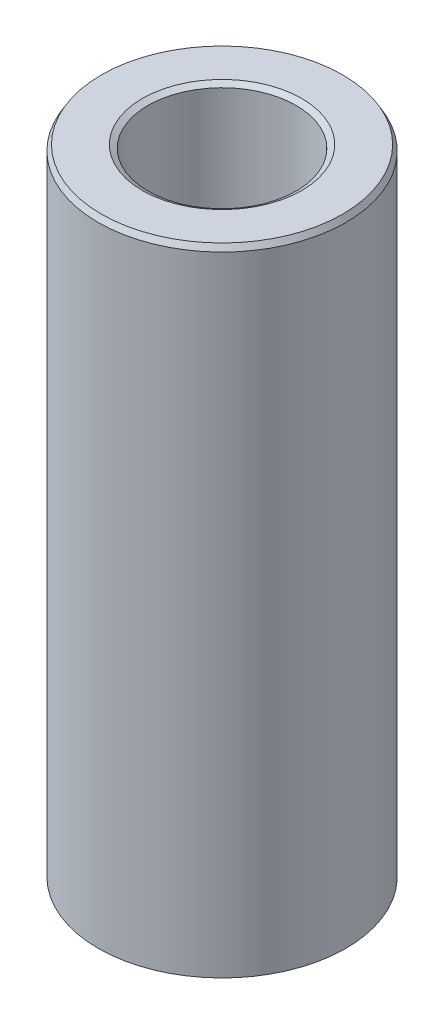
SolidWorks part; units mm, degrees
ref_plane "Front Plane" through (0, 0, 0) normal (0, 0, 1) x (1, 0, 0)
ref_plane "Top Plane" through (0, 0, 0) normal (0, 1, 0) x (1, 0, 0)
ref_plane "Right Plane" through (0, 0, 0) normal (1, 0, 0) x (0, 0, -1)
sketch "Sketch1" plane through (0, 0, 0) normal (0, 1, 0) x (1, 0, 0)
  circle A0 centre (0, 0) radius 55
  dimension "SLEEVE_OD" = 110
extrude "Boss-Extrude1" add sketch "Sketch1" along normal blind 283.0473
sketch "Sketch2" plane through (0, 0, 0) normal (0, 1, 0) x (1, 0, 0)
  circle A0 centre (0, 0) radius 32.9169
  dimension "BORE_D" = 65.8339
extrude "Cut-Extrude1" cut sketch "Sketch2" along normal through all
chamfer "Chamfer1" distance 2.486 angle 30 4 edges at (0, 283.0473, 32.9169) (0, 0, 32.9169) (0, 0, 55) (0, 283.0473, 55) first distance on face at (0, 283.0473, 32.9169) first distance on face at (0, 0, 32.9169) first distance on face at (0, 283.0473, 55)
